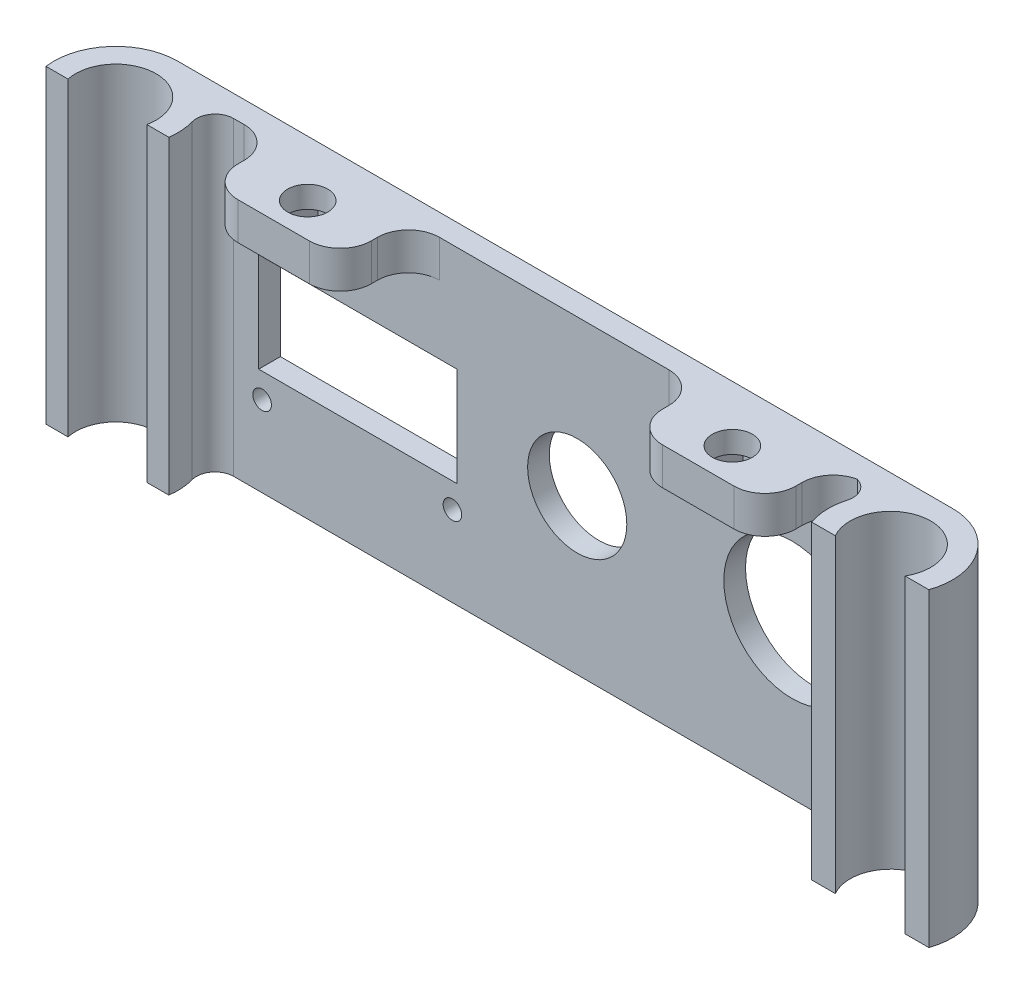
SolidWorks part; units mm, degrees
ref_plane "Front Plane" through (0, 0, 0) normal (0, 0, 1) x (1, 0, 0)
ref_plane "Top Plane" through (0, 0, 0) normal (0, 1, 0) x (1, 0, 0)
ref_plane "Right Plane" through (0, 0, 0) normal (1, 0, 0) x (0, 0, -1)
sketch "Sketch1" plane through (0, 0, 0) normal (0, 1, 0) x (1, 0, 0)
  line L0 (0, 0) -> (-124.96, 0)
  line L1 (-124.96, 10) -> (0, 10)
  line L2 (0, 10) -> (0, 6.5)
  line L3 (0, 6.5) -> (-124.96, 6.5)
  line L4 (-124.96, 0) -> (-124.96, -1.3505)
  line L5 (-124.96, -1.3505) -> (-140.8185, -1.3505)
  line L6 (-140.8185, -1.3505) -> (19.658, -1.3505)
  circle A0 centre (-124.96, 0) radius 6.5
  circle A1 centre (0, 0) radius 6.5
  circle A2 centre (-124.96, 0) radius 10
  circle A3 centre (0, 0) radius 10
extrude "Boss-Extrude2" add sketch "Sketch1" along normal blind 50 contours L6 A3 L2 A1 | L2 A3 L3 | A3 L1 A2 L3 | L3 A3 L0 A1 | L0 A3 L6 A1 | L0 A2 L3 A0 | L3 A2 L6 A0 region at (-117.9812, 0, -3.5511) region at (-6.9788, 0, -3.5511) region at (-8.2111, 0, 0.6768) region at (-62.48, 0, -8.2801) region at (-128.2659, 0, -5.6129) region at (-2.9305, 0, -7.9234) region at (5.6039, 0, -4.7615)
sketch "Sketch2" plane through (0, 50, 0) normal (0, 1, 0) x (1, 0, 0)
  line L0 (-62.48, 6.5) -> (-62.48, -4.5)
  line L1 (-62.48, -4.5) -> (-105.75, -4.5)
  line L2 (-7.5993, 6.5) -> (-117.3607, 6.5) construction
  line L3 (-62.48, -4.5) -> (-15.75, -4.5)
  line L4 (-105.75, -4.5) -> (-105.75, 6.5)
  line L5 (-105.75, 6.5) -> (-15.75, 6.5)
  line L6 (-15.75, 6.5) -> (-15.75, -4.5)
  line L7 (-118.46, 0) -> (-95, 0)
  line L8 (-6.5, 0) -> (-26.5, 0)
  line L9 (-95, 6.5) -> (-95, -4.5)
  line L10 (-26.5, 6.5) -> (-26.5, -4.5)
  line L11 (-105.75, -4.5) -> (-95, -4.5)
  line L12 (-95, -4.5) -> (-84.25, -4.5)
  line L13 (-26.5, -4.5) -> (-37.25, -4.5)
  line L14 (-37.25, -4.5) -> (-37.25, 6.5)
  line L15 (-37.25, 6.5) -> (-84.25, 6.5)
  line L16 (-84.25, 6.5) -> (-84.25, -4.5)
  line L17 (-134.8684, -1.3505) -> (-107.8559, -1.3505)
  arc A0 (6.3582, -1.3505) -> (-6.3582, -1.3505) centre (0, 0) ccw construction
  circle A3 centre (-95, 1) radius 3
  circle A4 centre (-26.5, 1) radius 3
  circle A5 centre (-124.96, 0) radius 6.5
  circle A6 centre (-124.96, 0) radius 10
  line M14 (-118.46, 0) -> (-114.96, 0)
  line M16 (-117.3607, 6.5) -> (-7.5993, 6.5)
extrude "Boss-Extrude3" add sketch "Sketch2" against normal blind 6 contours A3 L9 L1 L16 L5 | A3 L7 L4 L1 L9 | A3 L9 L4 L7 M16 | A4 L10 L5 L14 L3 | A4 L8 L6 L5 L10 | A4 L10 L3 L6 L8 | L17 A6 A5 M14 region at (-89.068, 50, -1) region at (-32.432, 50, -1) region at (-101.0512, 50, -3.5003) region at (-20.4488, 50, -3.5003) region at (-100.7706, 50, 2.3825) region at (-20.7294, 50, 2.3825) region at (-116.7489, 50, 0.6768)
sketch "Sketch3" plane through (0, 44, 0) normal (0, -1, 0) x (1, 0, 0)
  line L2 (-115.0516, 1.3505) -> (-118.6018, 1.3505)
  line L3 (-118.46, 0) -> (-114.96, 0)
  line L4 (-115.0516, 1.3505) -> (-118.6018, 1.3505)
  line L5 (-118.46, 0) -> (-114.96, 0)
  arc A2 (-118.46, 0) -> (-118.6018, 1.3505) centre (-124.96, 0) ccw
  arc A3 (-114.96, 0) -> (-115.0516, 1.3505) centre (-124.96, 0) ccw
  arc A4 (-118.46, 0) -> (-118.6018, 1.3505) centre (-124.96, 0) ccw
  arc A5 (-114.96, 0) -> (-115.0516, 1.3505) centre (-124.96, 0) ccw
  dimension "D1" = 0
extrude "Boss-Extrude4" add sketch "Sketch3" along normal up to surface (44 mm away) up to face at (-62.5446, 0, -3.7377)
fillet "Fillet1" radius 5 8 edges at (-105.75, 47, -6.5) (-84.25, 47, -6.5) (-37.25, 47, -6.5) (-15.75, 47, -6.5) (-15.75, 47, 4.5) (-37.25, 47, 4.5) (-84.25, 47, 4.5) (-105.75, 47, 4.5)
fillet "Fillet2" radius 3 2 edges at (-7.5993, 25, -6.5) (-117.3607, 25, -6.5)
sketch "Sketch5" plane through (0, 44, 0) normal (0, -1, 0) x (1, 0, 0)
  line L1 (-21.8969, -1) -> (-24.1984, 2.9864)
  line L2 (-24.1984, 2.9864) -> (-28.8016, 2.9864)
  line L3 (-28.8016, 2.9864) -> (-31.1031, -1)
  line L4 (-31.1031, -1) -> (-28.8016, -4.9864)
  line L5 (-28.8016, -4.9864) -> (-24.1984, -4.9864)
  line L6 (-24.1984, -4.9864) -> (-21.8969, -1)
  line L7 (-90.4012, -1) -> (-92.7006, 2.9827)
  line L8 (-92.7006, 2.9827) -> (-97.2994, 2.9827)
  line L9 (-97.2994, 2.9827) -> (-99.5988, -1)
  line L10 (-99.5988, -1) -> (-97.2994, -4.9827)
  line L11 (-97.2994, -4.9827) -> (-92.7006, -4.9827)
  line L12 (-92.7006, -4.9827) -> (-90.4012, -1)
  circle A2 centre (-26.5, -1) radius 3.9864 construction
  circle A3 centre (-95, -1) radius 3.9827 construction
extrude "Cut-Extrude3" cut sketch "Sketch5" against normal blind 2.5
sketch "Sketch6" plane through (0, 0, -10) normal (0, 0, -1) x (-1, 0, 0)
  line L0 (0, 25) -> (124.96, 25)
  line L1 (76.4046, 17) -> (108.4046, 17)
  line L2 (76.4046, 17) -> (76.4046, 32.9891)
  line L3 (76.4046, 32.9891) -> (108.4046, 32.9891)
  line L4 (108.4046, 17) -> (108.4046, 32.9891)
  line L5 (0, 50) -> (0, 0) construction
  line L6 (124.96, 50) -> (124.96, 0) construction
  line L7 (108.4046, 32.9891) -> (108.4046, 17)
  line L8 (76.4046, 17) -> (76.4046, 0)
  line L9 (124.96, 0) -> (0, 0) construction
  line L10 (108.4046, 17) -> (108.4046, 13)
  line L11 (92.4046, 17) -> (92.4046, 13)
  line L12 (92.4046, 13) -> (107.8546, 13)
  line L13 (92.4046, 13) -> (77.1546, 13)
  circle A0 centre (22.3762, 25) radius 11
  circle A1 centre (57.0266, 25) radius 8
  circle A2 centre (22.3762, 25) radius 16
  circle A3 centre (57.0266, 25) radius 11
  circle A4 centre (107.8546, 13) radius 1.5
  circle A5 centre (77.1546, 13) radius 1.5
  circle A6 centre (22.3762, 25) radius 12.5
extrude "Cut-Extrude7" cut sketch "Sketch6" against normal blind 65 contours L0 L4 L3 L2 | L1 L4 L0 L2 | A4 | A5 L8 | L8 A5 | L0 A1 | L0 A1 | L0 A0 | L0 A0 region at (-22.3762, 20.3315, -10) region at (-22.3762, 29.6685, -10) region at (-92.4046, 28.9946, -10) region at (-92.4046, 21, -10) region at (-57.0266, 28.3953, -10) region at (-57.0266, 21.6047, -10) region at (-77.8859, 14.2666, -10) region at (-76.0971, 13, -10) region at (-109.0595, 13.8202, -10)
sketch "Sketch7" plane through (0, 0, -6.5) normal (0, 0, 1) x (1, 0, 0)
  circle A0 centre (-22.3762, 25) radius 14
extrude "Cut-Extrude8" cut sketch "Sketch7" along normal blind 50
sketch "Sketch8" plane through (0, 50, 0) normal (0, 1, 0) x (1, 0, 0)
  circle A0 centre (-95, 1) radius 3.15
  circle A1 centre (-26.5, 1) radius 3.15
extrude "Cut-Extrude9" cut sketch "Sketch8" against normal blind 10
sketch "Sketch9" plane through (0, 50, 0) normal (0, 1, 0) x (1, 0, 0)
  line L0 (-131.2801, -2.0856) -> (9.7801, -2.0856)
  circle A0 centre (-124.96, 0) radius 6.5
  circle A1 centre (-124.96, 0) radius 6.6553
  circle A2 centre (0, 0) radius 6.5
  circle A3 centre (0, 0) radius 10
  line M10 (-9.9084, -1.3505) -> (-6.3582, -1.3505)
  line M12 (6.3582, -1.3505) -> (9.9084, -1.3505)
  line M16 (-134.8684, -1.3505) -> (-131.3182, -1.3505)
  line M18 (-118.6018, -1.3505) -> (-115.0516, -1.3505)
extrude "Boss-Extrude5" add sketch "Sketch9" against normal up to surface (50 mm away) contours A1 L0 A0 M16 | L0 A1 A0 M18 | A3 L0 A2 M10 | L0 A3 A2 M12 region at (-131.305, 50, 1.72) region at (-8.0567, 50, 1.7193) region at (-118.615, 50, 1.72) region at (8.0567, 50, 1.7193) up to face at (-62.48, 0, -3.5177)
sketch "Sketch10" plane through (0, 0, -6.5) normal (0, 0, 1) x (1, 0, 0)
  circle A0 centre (-22.3762, 25) radius 14
extrude "Cut-Extrude10" cut sketch "Sketch10" along normal blind 28
sketch "Sketch11" plane through (0, 0, 0) normal (0, -1, 0) x (1, 0, 0)
  line L0 (-130.9535, 3.2606) -> (9.4535, 3.2606)
  circle A0 centre (-124.96, 0) radius 6.823
  circle A1 centre (-124.96, 0) radius 6.5
  circle A2 centre (0, 0) radius 6.5
  circle A3 centre (0, 0) radius 10
  line M4 (9.7801, 2.0856) -> (6.1563, 2.0856)
  line M6 (-6.1563, 2.0856) -> (-9.7801, 2.0856)
  line M12 (-118.6399, 2.0856) -> (-118.8037, 2.0856)
  line M14 (-131.1163, 2.0856) -> (-131.2801, 2.0856)
extrude "Boss-Extrude6" add sketch "Sketch11" against normal up to surface (50 mm away) contours A3 L0 A2 M4 | L0 A3 A2 M6 | A1 A0 L0 M12 | A1 L0 A0 M14 region at (-130.7683, 0, 3.0909) region at (-7.7694, 0, 2.6785) region at (7.7694, 0, 2.6785) up to face at (-95, 50, 2.15)
sketch "Sketch12" plane through (0, 50, 0) normal (0, 1, 0) x (1, 0, 0)
  circle A0 centre (-95, 1) radius 3.23
  circle A1 centre (-26.5, 1) radius 3.23
extrude "Cut-Extrude11" cut sketch "Sketch12" against normal blind 10
sketch "Sketch13" plane through (0, 50, 0) normal (0, 1, 0) x (1, 0, 0)
  line L0 (-134.8684, -1.3505) -> (-115.0516, -1.3505)
  line L1 (-115.0516, -1.3505) -> (-115.0516, -5.9087)
  line L2 (-115.0516, -5.9087) -> (-134.8684, -5.9087)
  line L3 (-134.8684, -5.9087) -> (-134.8684, -1.3505)
extrude "Cut-Extrude12" cut sketch "Sketch13" against normal blind 70
